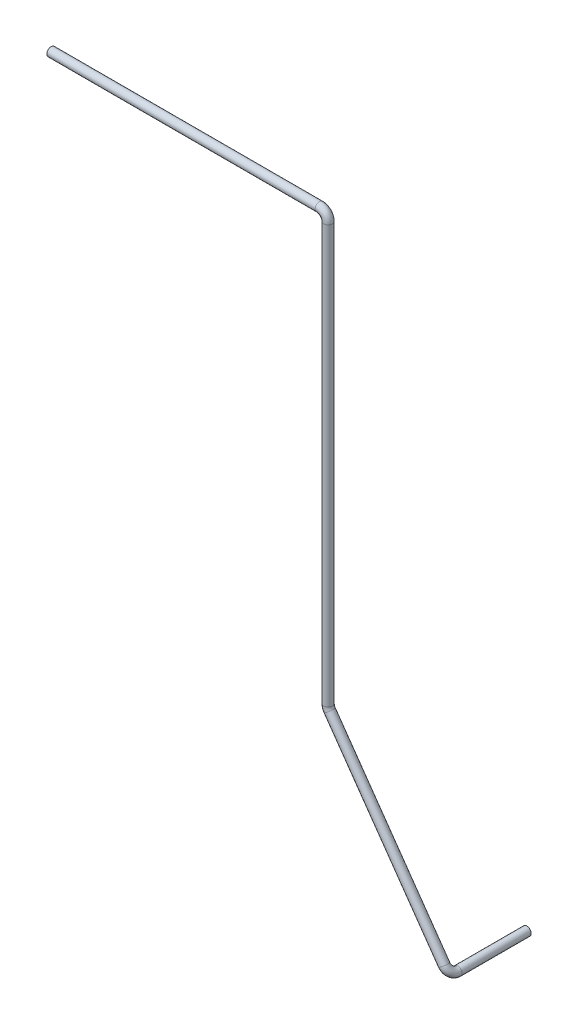
SolidWorks part; units mm, degrees
ref_plane "Plano frontal" through (0, 0, 0) normal (0, 0, 1) x (1, 0, 0)
ref_plane "Plano superior" through (0, 0, 0) normal (0, 1, 0) x (1, 0, 0)
ref_plane "Plano direito" through (0, 0, 0) normal (1, 0, 0) x (0, 0, -1)
sketch3d "3DSketch1"
  line L0 (-32572.9449, -14167.0136, 40791.8371) -> (-31243.2781, -14167.0136, 40791.8371) construction
  line L1 (-32582.9449, -14167.0136, 40791.8371) -> (-32572.9449, -14167.0136, 40791.8371) construction
  line L2 (-31243.2781, -14167.0136, 40791.8371) -> (-30310.464, -14167.0136, 40791.8371)
  line L3 (-30280.464, -14197.0136, 40791.8371) -> (-30280.464, -15648.7433, 40791.8371)
  line L4 (-30280.464, -15658.2169, 40791.8371) -> (-30280.464, -16257.8596, 40791.8371) construction
  line L5 (-30280.464, -16257.8596, 40791.8371) -> (-29859.7979, -16257.8596, 40791.8371) construction
  line L6 (-30275.0233, -15665.9724, 40791.8371) -> (-29877.0269, -16233.3002, 40791.8371)
  line L7 (-29859.7979, -16257.8596, 40761.8371) -> (-29859.7979, -16257.8596, 40521.7032)
  line L8 (-30135.8618, -16257.8596, 40521.7032) -> (-29859.7979, -16257.8596, 40521.7032) construction
  circle A0 centre (-30135.8618, -16257.8596, 40521.7032) radius 30.988 construction
  arc A1 (-29859.7979, -16257.8596, 40761.8371) -> (-29877.0269, -16233.3002, 40791.8371) centre (-29877.0269, -16233.3002, 40761.8371) ccw
  arc A2 (-30275.0233, -15665.9724, 40791.8371) -> (-30280.464, -15648.7433, 40791.8371) centre (-30250.464, -15648.7433, 40791.8371) ccw
  arc A3 (-30280.464, -14197.0136, 40791.8371) -> (-30310.464, -14167.0136, 40791.8371) centre (-30310.464, -14197.0136, 40791.8371) ccw
  point P13 (-30104.8738, -16257.8596, 40521.7032)
  point P18 (-29859.7979, -16257.8596, 40791.8371)
  point P20 (-29901.5862, -16250.5293, 40761.8371)
  point P23 (-30280.464, -15658.2169, 40791.8371)
  point P25 (-30250.464, -15648.7433, 40761.8371)
  point P28 (-30280.464, -14167.0136, 40791.8371)
  point P29 (-30310.464, -14197.0136, 40821.8371)
  dimension "D1" = 30
sweep "Sweep-Thin1" add path "3DSketch1" circular profile diameter 30 parameters "D1"=1, "D3"=30
